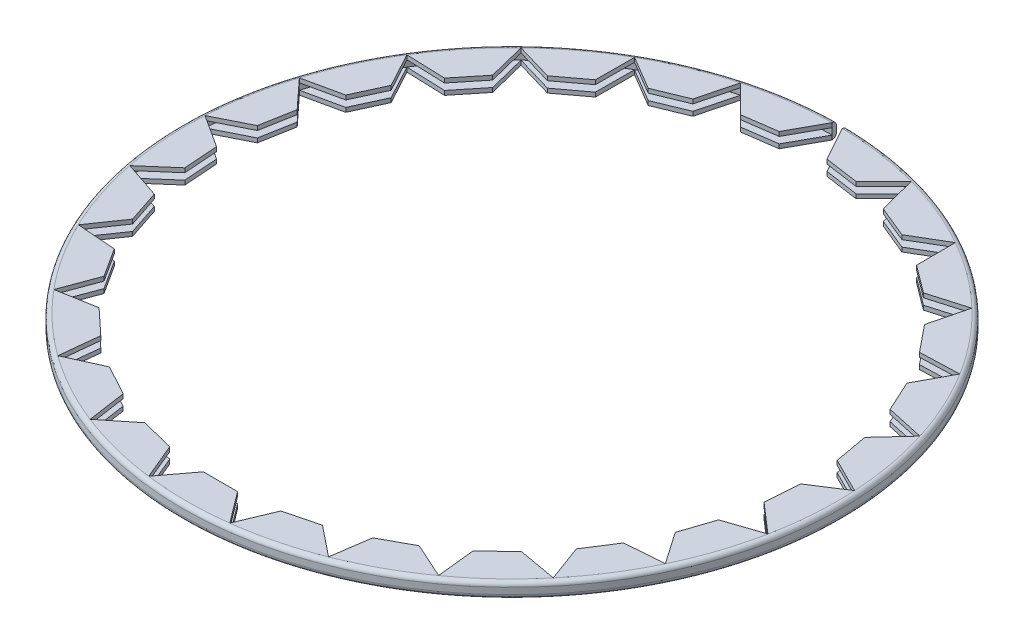
SolidWorks part; units mm, degrees
material "PC High Viscosity"
ref_plane "Front Plane" through (0, 0, 0) normal (0, 0, 1) x (1, 0, 0)
ref_plane "Top Plane" through (0, 0, 0) normal (0, 1, 0) x (1, 0, 0)
ref_plane "Right Plane" through (0, 0, 0) normal (1, 0, 0) x (0, 0, -1)
sketch "Sketch1" plane through (0, 0, 0) normal (0, 1, 0) x (1, 0, 0)
  circle A0 centre (0, 0) radius 244.475
  circle A1 centre (0, 0) radius 241.3
  dimension "D1" = 488.95
  dimension "D2" = 482.6
extrude "Boss-Extrude1" add sketch "Sketch1" along normal blind 11.1125
sketch "Sketch2" plane through (0, 0, 0) normal (0, 1, 0) x (1, 0, 0)
  line L2 (0, 0) -> (0, 386.7288) construction
  line L3 (-3.7465, 252.3652) -> (-3.7465, 199.5625)
  line L4 (-3.7465, 199.5625) -> (3.7465, 199.5625)
  line L5 (3.7465, 199.5625) -> (3.7465, 252.3652)
  line L6 (3.7465, 252.3652) -> (-3.7465, 252.3652)
  point P4 (0, 252.3652)
  dimension "D1" = 7.493
extrude "Cut-Extrude4" cut sketch "Sketch2" along normal through all contours L3 L4 L5 L6
sketch "Sketch3" plane through (0, 0, 0) normal (0, 1, 0) x (1, 0, 0)
  line L0 (-3.7465, 241.2709) -> (-17.7349, 215.9469)
  line L1 (-17.7349, 215.9469) -> (-42.8843, 212.3877)
  line L2 (-42.8843, 212.3877) -> (-63.3506, 232.8356)
  line L3 (0, 0) -> (-34.2575, 242.0629) construction
  line L4 (-17.7349, 215.9469) -> (-16.4151, 206.6206) construction
  line L5 (-34.2575, 242.0629) -> (23.8673, 250.2889) construction
  arc A0 (-3.7465, 241.2709) -> (3.7465, 241.2709) centre (0, 0) ccw construction
  arc A1 (-3.7465, 241.2709) -> (-63.3506, 232.8356) centre (0, 0) ccw
  arc A2 (-3.7465, 244.4463) -> (3.7465, 244.4463) centre (0, 0) ccw construction
  point P3 (-30.3096, 214.1673)
  dimension "D1" = 17.399
  dimension "D2" = 25.4
  dimension "D3" = 23.114
extrude "Boss-Extrude2" add sketch "Sketch3" along normal blind 11.1125
pattern_circular "CirPattern1" count 25 over 343.89 about axis through (0, 11.1125, 0) along (0, -1, 0) of "Boss-Extrude2" reverse direction yes
sketch "Sketch4" plane through (0, 0, 0) normal (1, 0, 0) x (0, 0, -1)
  line L0 (190.5, 7.9375) -> (241.3, 7.9375)
  line L1 (190.5, 7.9375) -> (190.5, 3.175)
  line L2 (241.3, 7.9375) -> (241.3, 3.175)
  line L3 (190.5, 3.175) -> (241.3, 3.175)
  line L4 (232.8283, 11.1125) -> (204.8399, 11.1125) construction
  line L5 (0, 0) -> (0, 46.4585) construction
  dimension "D1" = 3.175
  dimension "D2" = 241.3
  dimension "D3" = 4.7625
  dimension "D4" = 50.8
revolve "Cut-Revolve1" cut sketch "Sketch4" angle 360 about L5
fillet "Fillet1" radius 3.175 2 edges at (0, 0, 244.475) (0, 11.1125, 244.475)
